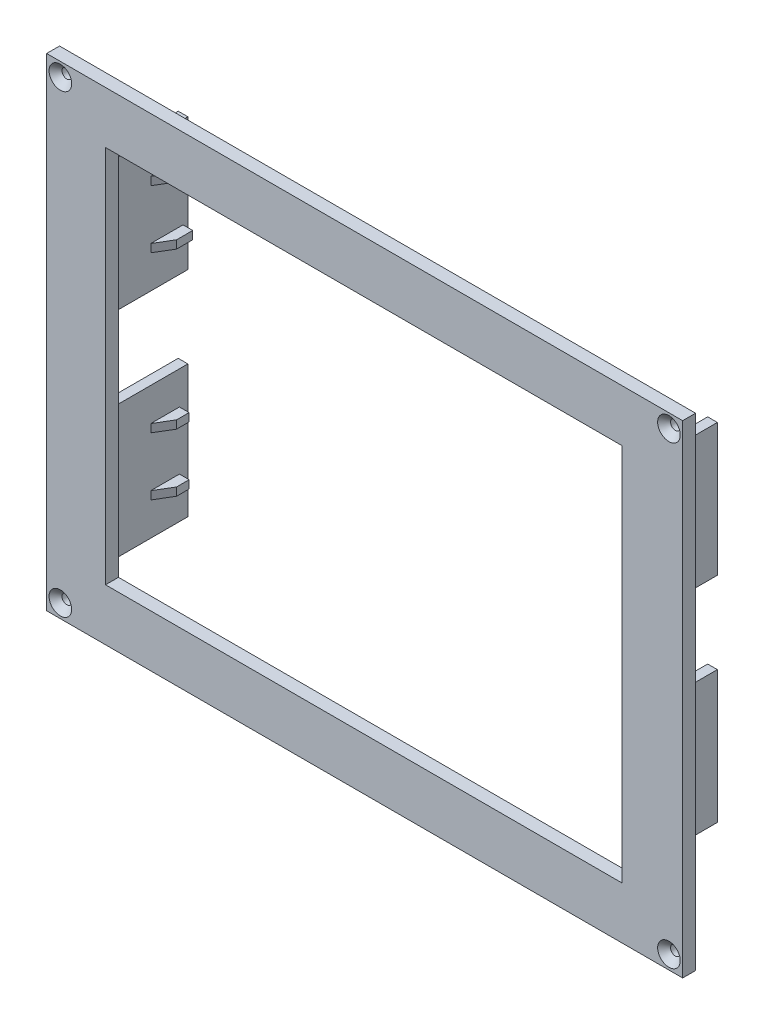
SolidWorks part; units mm, degrees
ref_plane "Plan de face" through (0, 0, 0) normal (0, 0, 1) x (1, 0, 0)
ref_plane "Plan de dessus" through (0, 0, 0) normal (0, 1, 0) x (1, 0, 0)
ref_plane "Plan de droite" through (0, 0, 0) normal (1, 0, 0) x (0, 0, -1)
sketch "Esquisse1" plane through (0, 0, 0) normal (0, 0, 1) x (1, 0, 0)
  line L1 (0, 0) -> (197, 0)
  line L2 (0, 0) -> (0, 149.5)
  line L3 (0, 149.5) -> (197, 149.5)
  line L4 (197, 0) -> (197, 149.5)
  dimension "D1" = 197
  dimension "D2" = 149.5
extrude "Boss.-Extru.1" add sketch "Esquisse1" along normal blind 4
sketch "Esquisse3" plane through (0, 0, 4) normal (0, 0, 1) x (1, 0, 0)
  line L0 (0, 149.5) -> (0, 0) construction
  line L1 (197, 149.5) -> (0, 149.5) construction
  line L2 (0, 0) -> (197, 0) construction
  line L3 (197, 0) -> (197, 149.5) construction
  circle A0 centre (4.25, 145.25) radius 1.5
  circle A2 centre (4.25, 4.25) radius 1.5
  circle A4 centre (192.75, 4.25) radius 1.5
  circle A6 centre (192.75, 145.25) radius 1.5
  dimension "D1" = 3
  dimension "D10" = 3
  dimension "D11" = 3
  dimension "D12" = 3
  dimension "D2" = 4.25
  dimension "D3" = 4.25
  dimension "D4" = 4.25
  dimension "D5" = 4.25
  dimension "D6" = 4.25
  dimension "D7" = 4.25
  dimension "D8" = 4.25
  dimension "D9" = 4.25
extrude "Enlèv. mat.-Extru.2" cut sketch "Esquisse3" against normal blind 4
chamfer "Chanfrein1" distance 2 angle 45 4 edges at (194.25, 145.25, 4) (194.25, 4.25, 4) (5.75, 4.25, 4) (5.75, 145.25, 4)
sketch "Esquisse4" plane through (0, 0, 4) normal (0, 0, 1) x (1, 0, 0)
  line L0 (197, 149.5) -> (0, 149.5) construction
  line L1 (18.25, 133.4) -> (178.25, 133.4)
  line L2 (18.25, 133.4) -> (18.25, 16.1)
  line L3 (18.25, 16.1) -> (178.25, 16.1)
  line L4 (178.25, 133.4) -> (178.25, 16.1)
  line L5 (0, 0) -> (197, 0) construction
  line L6 (0, 149.5) -> (0, 0) construction
  line L7 (197, 0) -> (197, 149.5) construction
  dimension "D1" = 117.3
  dimension "D2" = 160
  dimension "D3" = 16.1
  dimension "D4" = 16.1
  dimension "D5" = 18.25
  dimension "D6" = 18.75
extrude "Enlèv. mat.-Extru.3" cut sketch "Esquisse4" against normal blind 10
sketch "Esquisse5" plane through (0, 0, 0) normal (0, 0, -1) x (-1, 0, 0)
  line L2 (-178.75, 128.4) -> (-181.75, 128.4)
  line L3 (-178.75, 128.4) -> (-178.75, 87.4)
  line L4 (-178.75, 87.4) -> (-181.75, 87.4)
  line L5 (-181.75, 128.4) -> (-181.75, 87.4)
  line L6 (-18.25, 133.4) -> (-178.25, 133.4) construction
  line L7 (-178.25, 16.1) -> (-18.25, 16.1) construction
  line L8 (-178.75, 21.1) -> (-181.75, 21.1)
  line L9 (-178.75, 21.1) -> (-178.75, 62.1)
  line L10 (-178.75, 62.1) -> (-181.75, 62.1)
  line L11 (-181.75, 21.1) -> (-181.75, 62.1)
  line L12 (-178.25, 133.4) -> (-178.25, 16.1) construction
  line L13 (-18.25, 16.1) -> (-18.25, 133.4) construction
  line L14 (-17.75, 128.4) -> (-14.75, 128.4)
  line L15 (-17.75, 128.4) -> (-17.75, 87.4)
  line L16 (-17.75, 87.4) -> (-14.75, 87.4)
  line L17 (-14.75, 128.4) -> (-14.75, 87.4)
  line L18 (-17.75, 62.1) -> (-14.75, 62.1)
  line L19 (-17.75, 62.1) -> (-17.75, 21.1)
  line L20 (-17.75, 21.1) -> (-14.75, 21.1)
  line L21 (-14.75, 62.1) -> (-14.75, 21.1)
  dimension "D1" = 41
  dimension "D2" = 3
  dimension "D3" = 5
  dimension "D4" = 3
  dimension "D5" = 41
  dimension "D6" = 5
  dimension "D7" = 0.5
  dimension "D8" = 0.5
  dimension "D9" = 3
  dimension "D10" = 3
  dimension "D11" = 0.5
  dimension "D12" = 0.5
  dimension "D13" = 5
  dimension "D14" = 41
  dimension "D15" = 41
  dimension "D16" = 5
extrude "Boss.-Extru.2" add sketch "Esquisse5" along normal blind 22
sketch "Esquisse6" plane through (17.75, 0, 0) normal (1, 0, 0) x (0, 0, -1)
  line L0 (22, 128.4) -> (0, 128.4) construction
  line L1 (10.5, 118.15) -> (20.5, 118.15)
  line L2 (10.5, 118.15) -> (10.5, 115.65)
  line L3 (10.5, 115.65) -> (20.5, 115.65)
  line L4 (20.5, 118.15) -> (20.5, 115.65)
  line L5 (20.5, 100.15) -> (10.5, 100.15)
  line L6 (20.5, 100.15) -> (20.5, 97.65)
  line L7 (20.5, 97.65) -> (10.5, 97.65)
  line L8 (10.5, 100.15) -> (10.5, 97.65)
  line L9 (22, 87.4) -> (0, 87.4) construction
  line L10 (0, 128.4) -> (0, 87.4) construction
  line L11 (0, 62.1) -> (0, 21.1) construction
  line L12 (19.3828, 51.85) -> (10.5, 51.85)
  line L13 (19.3828, 51.85) -> (19.3828, 49.35)
  line L14 (19.3828, 49.35) -> (10.5, 49.35)
  line L15 (10.5, 51.85) -> (10.5, 49.35)
  line L16 (19.3828, 33.85) -> (10.5, 33.85)
  line L17 (19.3828, 33.85) -> (19.3828, 31.35)
  line L18 (19.3828, 31.35) -> (10.5, 31.35)
  line L19 (10.5, 33.85) -> (10.5, 31.35)
  line L20 (22, 21.1) -> (0, 21.1) construction
  line L21 (22, 62.1) -> (0, 62.1) construction
  dimension "D1" = 10.25
  dimension "D2" = 10.25
  dimension "D3" = 2.5
  dimension "D4" = 2.5
  dimension "D5" = 10.5
  dimension "D6" = 10.5
  dimension "D7" = 10
  dimension "D8" = 10
  dimension "D9" = 2.5
  dimension "D10" = 2.5
  dimension "D11" = 10.5
  dimension "D12" = 10.5
  dimension "D13" = 10.25
  dimension "D14" = 10.25
extrude "Boss.-Extru.3" add sketch "Esquisse6" along normal blind 3
sketch "Esquisse7" plane through (178.75, 0, 0) normal (-1, 0, 0) x (0, 0, 1)
  line L0 (-22, 128.4) -> (0, 128.4) construction
  line L1 (-20.5, 31.35) -> (-10.5, 31.35)
  line L2 (-20.5, 31.35) -> (-20.5, 33.85)
  line L3 (-20.5, 33.85) -> (-10.5, 33.85)
  line L4 (-10.5, 31.35) -> (-10.5, 33.85)
  line L5 (-20.5, 49.35) -> (-10.5, 49.35)
  line L6 (-20.5, 49.35) -> (-20.5, 51.85)
  line L7 (-20.5, 51.85) -> (-10.5, 51.85)
  line L8 (-10.5, 49.35) -> (-10.5, 51.85)
  line L9 (-20.5, 97.65) -> (-10.5, 97.65)
  line L10 (-20.5, 97.65) -> (-20.5, 100.15)
  line L11 (-20.5, 100.15) -> (-10.5, 100.15)
  line L12 (-10.5, 97.65) -> (-10.5, 100.15)
  line L13 (-20.5, 115.65) -> (-10.5, 115.65)
  line L14 (-20.5, 115.65) -> (-20.5, 118.15)
  line L15 (-20.5, 118.15) -> (-10.5, 118.15)
  line L16 (-10.5, 115.65) -> (-10.5, 118.15)
  line L17 (-22, 87.4) -> (0, 87.4) construction
  line L18 (-22, 62.1) -> (0, 62.1) construction
  line L19 (-22, 21.1) -> (0, 21.1) construction
  line L20 (0, 21.1) -> (0, 62.1) construction
  line L21 (0, 87.4) -> (0, 128.4) construction
  dimension "D1" = 2.5
  dimension "D2" = 2.5
  dimension "D3" = 2.5
  dimension "D4" = 2.5
  dimension "D5" = 10.25
  dimension "D6" = 10.25
  dimension "D7" = 10.25
  dimension "D8" = 10.25
  dimension "D9" = 10.5
  dimension "D10" = 10.5
  dimension "D11" = 10.5
  dimension "D12" = 10.5
  dimension "D13" = 10
  dimension "D14" = 10
  dimension "D15" = 10
  dimension "D16" = 10
extrude "Boss.-Extru.4" add sketch "Esquisse7" along normal blind 3
chamfer "Chanfrein2" distance 3 distance2 5 8 edges at (20.75, 98.9, -10.5) (20.75, 116.9, -10.5) (20.75, 32.6, -10.5) (20.75, 50.6, -10.5) (175.75, 116.9, -10.5) (175.75, 98.9, -10.5) (175.75, 50.6, -10.5) (175.75, 32.6, -10.5) first distance on face at (19.25, 98.9, -10.5) first distance on face at (19.25, 116.9, -10.5) first distance on face at (19.25, 32.6, -10.5) first distance on face at (19.25, 50.6, -10.5) first distance on face at (177.25, 116.9, -10.5) first distance on face at (177.25, 98.9, -10.5) first distance on face at (177.25, 50.6, -10.5) first distance on face at (177.25, 32.6, -10.5)
